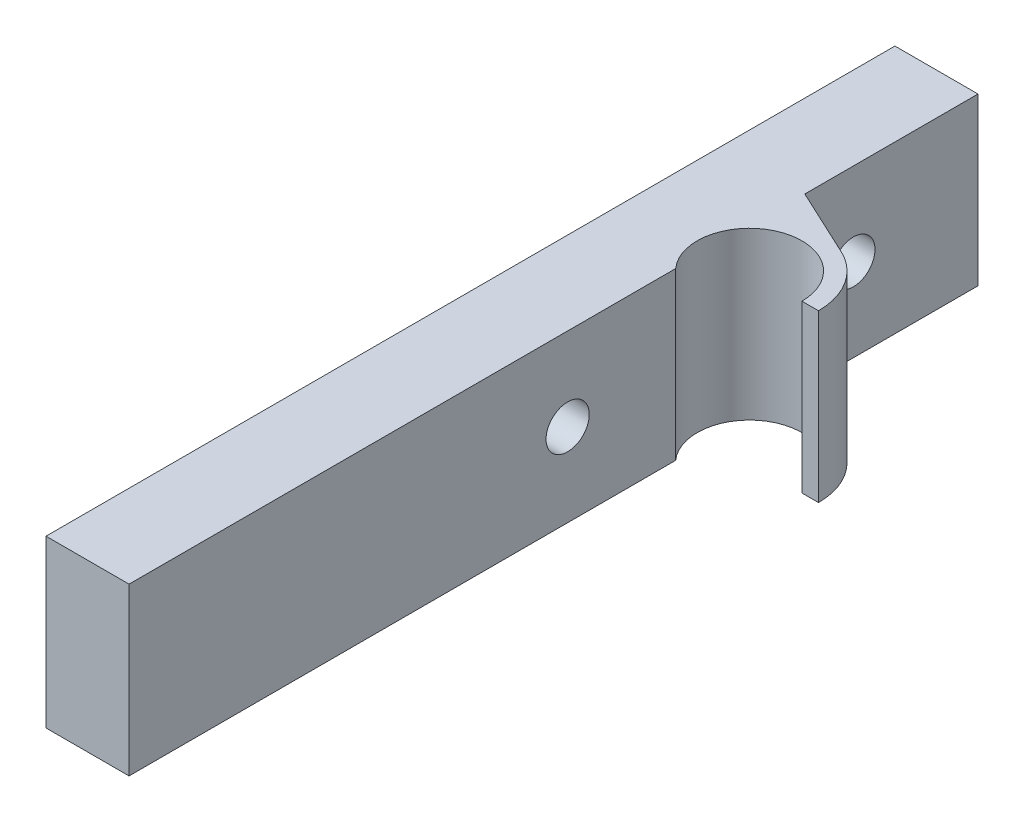
SolidWorks part; units mm, degrees
other "General Table1"
other "DetailItem1"
material "Custom Plastic"
ref_plane "X-Y Datum" through (0, 0, 0) normal (0, 0, 1) x (1, 0, 0)
ref_plane "X-Z Datum" through (0, 0, 0) normal (0, 1, 0) x (1, 0, 0)
ref_plane "Y-Z Datum" through (0, 0, 0) normal (1, 0, 0) x (0, 0, -1)
sketch "Sketch3" plane through (0, 0, 0) normal (0, 1, 0) x (1, 0, 0)
  line L0 (8.001, 0) -> (-8.001, 0) construction
  line L1 (0, 8.001) -> (0, -8.001) construction
  line L2 (8.001, 0) -> (10.541, 0)
  line L3 (-8.001, 0) -> (-10.541, 0) construction
  line L4 (-5.969, 8.6881) -> (-5.969, -8.6881) construction
  line L5 (0, 8.001) -> (0, 21.844) construction
  line L6 (0, -8.001) -> (0, -21.844) construction
  line L7 (-5.969, -8.6881) -> (-5.969, -21.844) construction
  line L8 (0, 21.844) -> (-5.969, 21.844) construction
  line L9 (-5.969, 8.6881) -> (-5.969, 21.844) construction
  line L10 (0, -21.844) -> (-5.969, -21.844) construction
  line L11 (-5.969, 21.844) -> (-18.669, 21.844) construction
  line L12 (-5.969, 0) -> (-18.669, 0)
  line L13 (-5.969, 0) -> (-5.969, 40.894)
  line L14 (-5.969, 40.894) -> (-18.669, 40.894)
  line L15 (-18.669, 0) -> (-18.669, 40.894)
  line L16 (4.4548, 9.5534) -> (-5.969, 14.4141)
  line L17 (-5.969, 0) -> (-18.669, 0)
  line L18 (-5.969, 0) -> (-5.969, -88.9)
  line L19 (-5.969, -88.9) -> (-18.669, -88.9)
  line L20 (-18.669, 0) -> (-18.669, -88.9)
  line L21 (-5.969, -21.844) -> (-18.669, -21.844) construction
  circle A0 centre (0, 0) radius 7.9375 construction
  circle A2 centre (0, 0) radius 8.001
  circle A3 centre (0, 0) radius 10.541
  point P4 (-7.9375, 0)
  point P7 (0, 0)
  point P8 (0, -7.9375)
  point P11 (0, 0)
  point P12 (7.9375, 0)
  point P13 (0, 7.9375)
  point P20 (-5.969, 0)
  point P28 (0, -10.541)
  point P29 (0, 10.541)
  dimension "D3" = 21.082
  dimension "D4" = 2.032
  dimension "D6" = 12.7
  dimension "D7" = 19.05
  dimension "D8" = 65
  dimension "D9" = 88.9
extrude "Boss-Extrude1" add sketch "Sketch3" along normal blind 12.7 and the other way blind 12.7 contours L17 A3 L18 A2 | L13 A3 L17 A2 | A3 L13 L14 L15 L12 | A3 L13 A2 L2 | A3 L12 L20 L19 L18 | A3 L16 L13 region at (2.9209, 0, -7.6588) region at (-8.2158, 0, -3.865) region at (-8.2158, 0, 3.865) region at (-3.3238, 0, -11.4774) region at (-12.4325, 0, 45.4905) region at (-12.5734, 0, -21.4158)
sketch "Sketch5" plane through (-18.669, 0, 0) normal (-1, 0, 0) x (0, 0, 1)
  line L0 (0, -12.7) -> (0, 12.7) construction
  line L1 (-40.894, 12.7) -> (88.9, 12.7) construction
  circle A0 centre (-21.844, 0) radius 3.175 construction
  circle A1 centre (-21.844, 0) radius 3.302
  circle A2 centre (21.844, 0) radius 3.175 construction
  circle A3 centre (21.844, 0) radius 3.302
  point P0 (-21.844, 0)
  point P1 (21.844, 0)
  point P5 (0, 0)
  point P15 (0, 0)
  dimension "D1" = 6.35
  dimension "D2" = 6.604
  dimension "D3" = 6.35
  dimension "D4" = 6.604
extrude "Cut-Extrude1" cut sketch "Sketch5" against normal through all and the other way through all
ref_axis "Axis Chassis Tube X" through (110.7012, -6.6453, 57.15) along (-1, 0, 0)
ref_axis "Axis Chassis Tube Y" through (32.122, -70.0611, 57.15) along (0, 1, 0)
ref_point "Point Chassis Tube XYZ Intersection"
ref_axis "Axis Chassis Tube Z" through (32.122, 25.3343, -217.8748) along (0, -0.1155, 0.9933)
sketch "Sketch7" plane through (0, -12.7, 0) normal (0, -1, 0) x (1, 0, 0)
  line L0 (-18.669, 57.15) -> (-5.969, 57.15)
  line L1 (-18.669, 0) -> (-18.669, 88.9) construction
  line L2 (110.7012, 57.15) -> (-88.9779, 57.15) construction
  line L3 (-5.969, 0) -> (-5.969, 88.9) construction
ref_plane "Plane1" through (32.122, -6.6453, 57.15) normal (0, 1, 0) x (1, 0, 0)
ref_plane "Plane2" through (32.122, -6.6453, 57.15) normal (-1, 0, 0) x (0, 0, 1)
ref_plane "Plane3" through (32.122, -6.6453, 57.15) normal (0, -0.1155, 0.9933) x (1, 0, 0)
sketch "Sketch8" plane through (32.122, -6.6453, 57.15) normal (0, 1, 0) x (1, 0, 0)
  line L0 (0, 55) -> (0, -55) construction
  circle A0 centre (0, 0) radius 12.7
  dimension "D1" = 25.4
equation "\"Torsion Bar OD Clearance\"= 0.005"
equation "\"Torsion Bar OD Fit Size\"= 5 / 8in + \"Torsion Bar OD Clearance\""
equation "\"D2@Sketch3\"=\"Torsion Bar OD Fit Size\""
equation "\"TB Hook Thickness\" = 0.40"
equation "\"TB Hook OD\" = \"Torsion Bar OD Fit Size\" + \"TB Hook Thickness\" / 2"
equation "\"D3@Sketch3\"=\"TB Hook OD\""
equation "\"TB OD Clearance Depth\" = 0.080"
equation "\"D4@Sketch3\"=\"TB OD Clearance Depth\""
equation "\"Lower Jig thickness\"=0.5"
equation "\"D6@Sketch3\"=\"Lower Jig thickness\""
equation "\"Lower Jig Width\"= 1.0"
equation "\"D1@Boss-Extrude1\"=\"Lower Jig Width\"/2"
equation "\"D2@Boss-Extrude1\"=\"Lower Jig Width\"/2"
equation "\"Weld Stud OD\" = 0.25"
equation "\"Weld Stud Clearance\" = 0.01"
equation "\"D1@Sketch5\"=\"Weld Stud OD\""
equation "\"D2@Sketch5\"=\"Weld Stud OD\"+\"Weld Stud Clearance\""
equation "\"D3@Sketch5\"=\"Weld Stud OD\""
